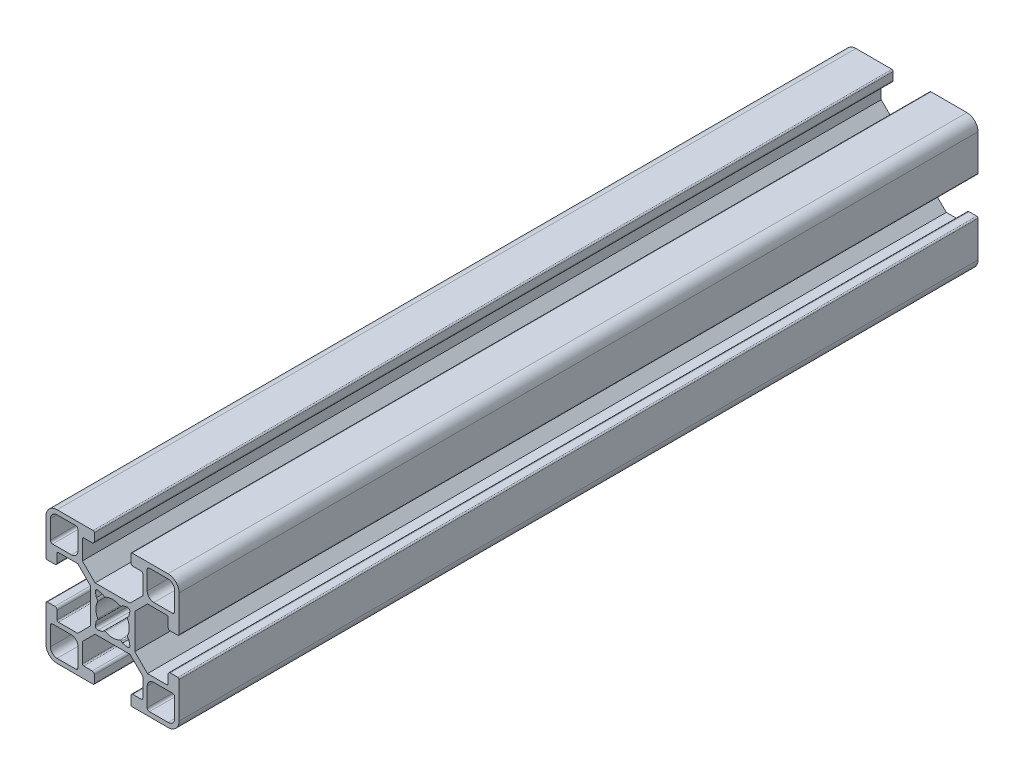
SolidWorks part; units mm, degrees
ref_plane "Front Plane" through (0, 0, 0) normal (0, 0, 1) x (1, 0, 0)
ref_plane "Top Plane" through (0, 0, 0) normal (0, 1, 0) x (1, 0, 0)
ref_plane "Right Plane" through (0, 0, 0) normal (1, 0, 0) x (0, 0, -1)
sketch "Sketch1" plane through (0, 0, 0) normal (0, 0, 1) x (1, 0, 0)
  line L0 (18.8789, 11.7141) -> (18.6573, 12.7569)
  line L1 (11.3427, 17.2431) -> (11.1211, 18.2859)
  line L2 (12.9949, 18.4193) -> (12.7569, 18.6573)
  line L3 (21.8, 7.1394) -> (18.9393, 10)
  line L4 (22.8607, 8.2) -> (20, 11.0607)
  line L5 (11.5807, 17.0051) -> (11.3427, 17.2431)
  line L6 (17.2431, 11.3427) -> (17.0051, 11.5806)
  line L7 (10, 18.9393) -> (7.1393, 21.8)
  line L8 (11.0607, 20) -> (8.2, 22.8607)
  line L9 (18.6573, 12.7569) -> (18.4193, 12.9948)
  line L10 (18.2859, 11.1211) -> (17.2431, 11.3427)
  line L11 (12.7569, 18.6573) -> (11.7141, 18.8789)
  line L12 (2.5, 0) -> (10.6, 0)
  line L13 (19.4, 0) -> (27.5, 0)
  line L14 (23.3, 1) -> (27.5, 1)
  line L15 (2.5, 1) -> (6.7, 1)
  line L16 (8.5, 2.5) -> (10.4, 2.5)
  line L17 (19.6, 2.5) -> (21.5, 2.5)
  line L18 (24.3, 7.2) -> (28.5, 7.2)
  line L19 (1.5, 7.2) -> (5.7, 7.2)
  line L20 (2.8, 8.2) -> (7.1393, 8.2)
  line L21 (22.8607, 8.2) -> (27.2, 8.2)
  line L22 (11.0607, 10) -> (18.9393, 10)
  line L23 (0.3, 10.9) -> (2, 10.9)
  line L24 (28, 10.9) -> (29.7, 10.9)
  line L25 (0.3, 19.1) -> (2, 19.1)
  line L26 (28, 19.1) -> (29.7, 19.1)
  line L27 (11.0607, 20) -> (18.9393, 20)
  line L28 (2.8, 21.8) -> (7.1393, 21.8)
  line L29 (22.8607, 21.8) -> (27.2, 21.8)
  line L30 (1.5, 22.8) -> (5.7, 22.8)
  line L31 (24.3, 22.8) -> (28.5, 22.8)
  line L32 (19.6, 27.5) -> (21.5, 27.5)
  line L33 (8.5, 27.5) -> (10.4, 27.5)
  line L34 (2.5, 29) -> (6.7, 29)
  line L35 (23.3, 29) -> (27.5, 29)
  line L36 (19.4, 30) -> (27.5, 30)
  line L37 (2.5, 30) -> (10.6, 30)
  line L38 (11.7141, 11.1211) -> (12.7569, 11.3427)
  line L39 (17.2431, 18.6573) -> (18.2859, 18.8789)
  line L40 (18.4194, 17.0051) -> (18.6573, 17.2431)
  line L41 (8.2, 7.1393) -> (11.0607, 10)
  line L42 (7.1393, 8.2) -> (10, 11.0607)
  line L43 (12.7569, 11.3427) -> (12.9949, 11.5806)
  line L44 (11.3427, 12.7569) -> (11.5807, 12.9949)
  line L45 (20, 18.9393) -> (22.8607, 21.8)
  line L46 (18.9393, 20) -> (21.8, 22.8607)
  line L47 (17.0051, 18.4193) -> (17.2431, 18.6573)
  line L48 (11.1211, 11.7141) -> (11.3427, 12.7569)
  line L49 (18.6573, 17.2431) -> (18.8789, 18.2859)
  line L50 (0, 19.4) -> (0, 27.5)
  line L51 (0, 2.5) -> (0, 10.6)
  line L52 (1, 23.3) -> (1, 27.5)
  line L53 (1, 2.5) -> (1, 6.7)
  line L54 (2.5, 8.5) -> (2.5, 10.4)
  line L55 (2.5, 19.6) -> (2.5, 21.5)
  line L56 (7.2, 24.3) -> (7.2, 28.5)
  line L57 (7.2, 1.5) -> (7.2, 5.7)
  line L58 (8.2, 2.8) -> (8.2, 7.1393)
  line L59 (8.2, 22.8607) -> (8.2, 27.2)
  line L60 (10, 11.0607) -> (10, 18.9393)
  line L61 (10.9, 0.3) -> (10.9, 2)
  line L62 (10.9, 28) -> (10.9, 29.7)
  line L63 (19.1, 0.3) -> (19.1, 2)
  line L64 (19.1, 28) -> (19.1, 29.7)
  line L65 (20, 11.0607) -> (20, 18.9393)
  line L66 (21.8, 2.8) -> (21.8, 7.1394)
  line L67 (21.8, 22.8607) -> (21.8, 27.2)
  line L68 (22.8, 24.3) -> (22.8, 28.5)
  line L69 (22.8, 1.5) -> (22.8, 5.7)
  line L70 (27.5, 8.5) -> (27.5, 10.4)
  line L71 (27.5, 19.6) -> (27.5, 21.5)
  line L72 (29, 23.3) -> (29, 27.5)
  line L73 (29, 2.5) -> (29, 6.7)
  line L74 (30, 2.5) -> (30, 10.6)
  line L75 (30, 19.4) -> (30, 27.5)
  arc A0 (0.3, 10.9) -> (0, 10.6) centre (0.3, 10.6) ccw
  arc A1 (0, 19.4) -> (0.3, 19.1) centre (0.3, 19.4) ccw
  arc A2 (1.5, 7.2) -> (1, 6.7) centre (1.5, 6.7) ccw
  arc A3 (1, 23.3) -> (1.5, 22.8) centre (1.5, 23.3) ccw
  arc A4 (2.5, 10.4) -> (2, 10.9) centre (2, 10.4) ccw
  arc A5 (2, 19.1) -> (2.5, 19.6) centre (2, 19.6) ccw
  arc A6 (1, 2.5) -> (2.5, 1) centre (2.5, 2.5) ccw
  arc A7 (0, 2.5) -> (2.5, 0) centre (2.5, 2.5) ccw
  arc A8 (2.5, 29) -> (1, 27.5) centre (2.5, 27.5) ccw
  arc A9 (2.5, 30) -> (0, 27.5) centre (2.5, 27.5) ccw
  arc A10 (2.5, 8.5) -> (2.8, 8.2) centre (2.8, 8.5) ccw
  arc A11 (2.8, 21.8) -> (2.5, 21.5) centre (2.8, 21.5) ccw
  arc A12 (7.2, 5.7) -> (5.7, 7.2) centre (5.7, 5.7) ccw
  arc A13 (5.7, 22.8) -> (7.2, 24.3) centre (5.7, 24.3) ccw
  arc A14 (6.7, 1) -> (7.2, 1.5) centre (6.7, 1.5) ccw
  arc A15 (7.2, 28.5) -> (6.7, 29) centre (6.7, 28.5) ccw
  arc A16 (8.2, 2.8) -> (8.5, 2.5) centre (8.5, 2.8) ccw
  arc A17 (8.5, 27.5) -> (8.2, 27.2) centre (8.5, 27.2) ccw
  arc A18 (10.9, 2) -> (10.4, 2.5) centre (10.4, 2) ccw
  arc A19 (10.4, 27.5) -> (10.9, 28) centre (10.4, 28) ccw
  arc A20 (10.6, 0) -> (10.9, 0.3) centre (10.6, 0.3) ccw
  arc A21 (10.9, 29.7) -> (10.6, 30) centre (10.6, 29.7) ccw
  arc A22 (11.5807, 12.9949) -> (11.6375, 13.3398) centre (11.3685, 13.207) ccw
  arc A23 (11.6375, 16.6602) -> (11.5807, 17.0051) centre (11.3685, 16.793) ccw
  arc A24 (11.1211, 11.7141) -> (11.7141, 11.1211) centre (11.6102, 11.6102) ccw
  arc A25 (11.7141, 18.8789) -> (11.1211, 18.2859) centre (11.6102, 18.3898) ccw
  arc A26 (13.3398, 11.6375) -> (12.9949, 11.5806) centre (13.207, 11.3685) ccw
  arc A27 (12.9949, 18.4193) -> (13.3398, 18.3625) centre (13.207, 18.6315) ccw
  arc A28 (11.6375, 16.6602) -> (11.6375, 13.3398) centre (15, 15) ccw
  arc A29 (16.6602, 18.3625) -> (13.3398, 18.3625) centre (15, 15) ccw
  arc A30 (18.3625, 13.3398) -> (18.3625, 16.6602) centre (15, 15) ccw
  arc A31 (13.3398, 11.6375) -> (16.6602, 11.6375) centre (15, 15) ccw
  arc A32 (17.0051, 11.5806) -> (16.6602, 11.6375) centre (16.793, 11.3685) ccw
  arc A33 (16.6602, 18.3625) -> (17.0051, 18.4193) centre (16.793, 18.6315) ccw
  arc A34 (18.2859, 11.1211) -> (18.8789, 11.7141) centre (18.3898, 11.6102) ccw
  arc A35 (18.8789, 18.2859) -> (18.2859, 18.8789) centre (18.3898, 18.3898) ccw
  arc A36 (18.3625, 13.3398) -> (18.4193, 12.9948) centre (18.6315, 13.207) ccw
  arc A37 (18.4194, 17.0051) -> (18.3625, 16.6602) centre (18.6315, 16.793) ccw
  arc A38 (19.1, 0.3) -> (19.4, 0) centre (19.4, 0.3) ccw
  arc A39 (19.4, 30) -> (19.1, 29.7) centre (19.4, 29.7) ccw
  arc A40 (19.6, 2.5) -> (19.1, 2) centre (19.6, 2) ccw
  arc A41 (19.1, 28) -> (19.6, 27.5) centre (19.6, 28) ccw
  arc A42 (21.5, 2.5) -> (21.8, 2.8) centre (21.5, 2.8) ccw
  arc A43 (21.8, 27.2) -> (21.5, 27.5) centre (21.5, 27.2) ccw
  arc A44 (22.8, 1.5) -> (23.3, 1) centre (23.3, 1.5) ccw
  arc A45 (23.3, 29) -> (22.8, 28.5) centre (23.3, 28.5) ccw
  arc A46 (24.3, 7.2) -> (22.8, 5.7) centre (24.3, 5.7) ccw
  arc A47 (22.8, 24.3) -> (24.3, 22.8) centre (24.3, 24.3) ccw
  arc A48 (27.2, 8.2) -> (27.5, 8.5) centre (27.2, 8.5) ccw
  arc A49 (27.5, 21.5) -> (27.2, 21.8) centre (27.2, 21.5) ccw
  arc A50 (27.5, 1) -> (29, 2.5) centre (27.5, 2.5) ccw
  arc A51 (27.5, 0) -> (30, 2.5) centre (27.5, 2.5) ccw
  arc A52 (29, 27.5) -> (27.5, 29) centre (27.5, 27.5) ccw
  arc A53 (30, 27.5) -> (27.5, 30) centre (27.5, 27.5) ccw
  arc A54 (28, 10.9) -> (27.5, 10.4) centre (28, 10.4) ccw
  arc A55 (27.5, 19.6) -> (28, 19.1) centre (28, 19.6) ccw
  arc A56 (29, 6.7) -> (28.5, 7.2) centre (28.5, 6.7) ccw
  arc A57 (28.5, 22.8) -> (29, 23.3) centre (28.5, 23.3) ccw
  arc A58 (30, 10.6) -> (29.7, 10.9) centre (29.7, 10.6) ccw
  arc A59 (29.7, 19.1) -> (30, 19.4) centre (29.7, 19.4) ccw
extrude "Boss-Extrude1" add sketch "Sketch1" along normal mid plane 180
equation "\"LENGTH\"=500"
